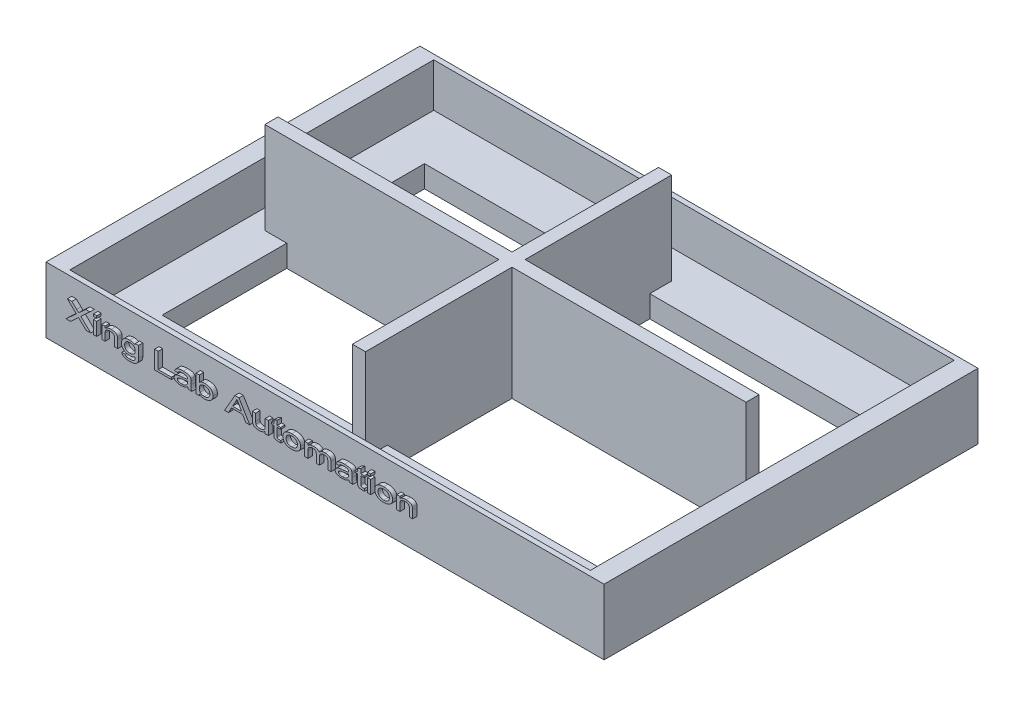
SolidWorks part; units mm, degrees
ref_plane "前视基准面" through (0, 0, 0) normal (0, 0, 1) x (1, 0, 0)
ref_plane "上视基准面" through (0, 0, 0) normal (0, 1, 0) x (1, 0, 0)
ref_plane "右视基准面" through (0, 0, 0) normal (1, 0, 0) x (0, 0, -1)
other "Configuration Table"
sketch "草图1" plane through (0, 0, 0) normal (0, 1, 0) x (1, 0, 0)
  line L0 (-59.5, 42.75) -> (-59.5, -42.7501)
  line L1 (-63.8, -42.75) -> (63.8, -42.75)
  line L3 (-63.8, 42.75) -> (63.8, 42.75)
  line L4 (63.8, -42.75) -> (63.8, 42.75)
  line L5 (-63.8, -42.75) -> (63.8, 42.75) construction
  line L6 (-63.8, 42.75) -> (63.8, -42.75) construction
  line L8 (-63.8, 42.75) -> (-63.8, -42.75)
  line L15 (-59.5, -41.6001) -> (59.5, -41.6001)
  line L17 (-59.5, -42.7501) -> (59.5, -42.7501)
  line L21 (-59.5, 41.6049) -> (59.5, 41.6049)
  line L23 (-50, -30) -> (50, -30)
  line L24 (-50, -30) -> (-50, 30)
  line L25 (-50, 30) -> (50, 30)
  line L26 (50, -30) -> (50, 30)
  line L27 (-50, -30) -> (50, 30) construction
  line L28 (-50, 30) -> (50, -30) construction
  line L30 (1.5, -30) -> (1.5, 30)
  line L32 (-1.5, -30) -> (-1.5, 30)
  line L33 (1.5, -30) -> (-1.5, 30) construction
  line L34 (1.5, 30) -> (-1.5, -30) construction
  line L35 (50, 1.5) -> (-50, 1.5)
  line L37 (50, -1.5) -> (-50, -1.5)
  line L39 (50, 1.5) -> (-50, -1.5) construction
  line L40 (50, -1.5) -> (-50, 1.5) construction
  line L41 (59.5, 42.75) -> (59.5, -42.7501)
  line L43 (-50, 1.5) -> (50, 1.5)
  line L44 (-50, 1.5) -> (-50, -1.5)
  line L45 (-50, -1.5) -> (50, -1.5)
  line L46 (50, 1.5) -> (50, -1.5)
  line L47 (-50, 1.5) -> (-55, 1.5)
  line L48 (-50, 1.5) -> (-50, -1.5)
  line L49 (-50, -1.5) -> (-55, -1.5)
  line L50 (-55, 1.5) -> (-55, -1.5)
  line L51 (50, 1.5) -> (55, 1.5)
  line L52 (50, 1.5) -> (50, -1.5)
  line L53 (50, -1.5) -> (55, -1.5)
  line L54 (55, 1.5) -> (55, -1.5)
  line L55 (-1.5, 30) -> (1.5, 30)
  line L56 (-1.5, 30) -> (-1.5, 35)
  line L57 (-1.5, 35) -> (1.5, 35)
  line L58 (1.5, 30) -> (1.5, 35)
  line L59 (1.5, -30) -> (-1.5, -30)
  line L60 (1.5, -30) -> (1.5, -35)
  line L61 (1.5, -35) -> (-1.5, -35)
  line L62 (-1.5, -30) -> (-1.5, -35)
  point P0 (0, 0)
  point P18 (0, 0)
  point P23 (0, 0)
  point P28 (0, 0)
  dimension "D1" = 127.6
  dimension "D2" = 85.5
  dimension "D7" = 119
  dimension "D8" = 1.15
  dimension "D9" = 60
  dimension "D10" = 100
  dimension "D11" = 100
extrude "凸台-拉伸2" add sketch "草图1" along normal blind 5 contours L21 L15 L26 L23 L24 L25 region at (0, 0, -40.1529)
extrude "凸台-拉伸3" add sketch "草图1<4>" along normal blind 15 contours L3 L1 | L21 L3 | L3 L1 L4 | L15 L1 region at (0, 0, -42.1774) region at (-61.65, 0, 0) region at (61.65, 0, 0) region at (0, 0, 42.1751)
sketch "草图1<4>" plane through (0, 0, 0) normal (0, 1, 0) x (1, 0, 0) same geometry as "草图1"
sketch "草图2" plane through (0, 0, 42.75) normal (0, 0, 1) x (1, 0, 0)
  text T0 "Xing Lab Automation" font "Helvetica" height in points 16
extrude "凸台-拉伸4" add sketch "草图2" along normal blind 1
extrude "凸台-拉伸11" add sketch "草图1<9>" along normal blind 26 contours L37 L32 L35 L24 | L47 L50 L49 L24 | L37 L30 L35 L32 | L37 L26 L35 L30 | L54 L51 L26 L53 | L30 L37 L32 L23 | L23 L62 L61 L60 | L35 L30 L25 L32 | L25 L58 L57 L56 region at (0, 0, 15.75) region at (0, 0, 32.5) region at (-52.5, 0, 0) region at (-25.75, 0, 0) region at (0, 0, 0) region at (25.75, 0, 0) region at (0, 0, -15.75) region at (52.5, 0, 0) region at (0, 0, -32.5)
sketch "草图1<9>" plane through (0, 0, 0) normal (0, 1, 0) x (1, 0, 0) same geometry as "草图1"
